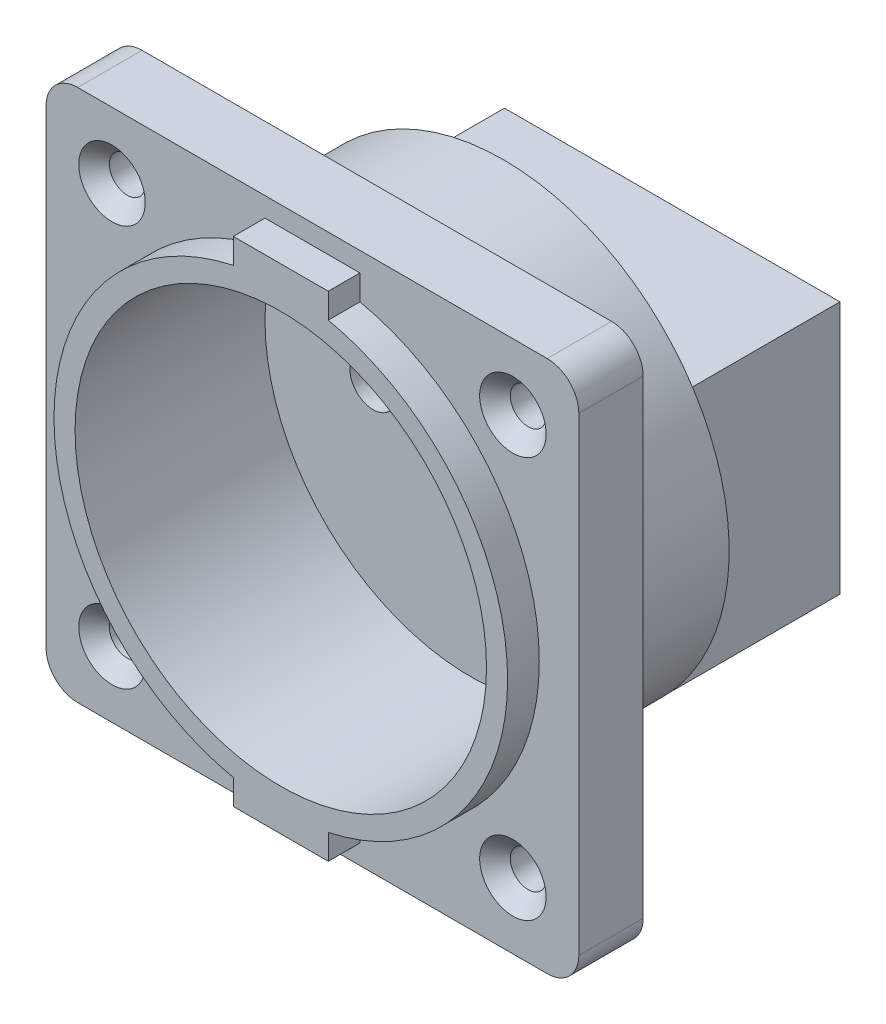
SolidWorks part; units mm, degrees
material "ABS"
ref_plane "Ebene vorne" through (0, 0, 0) normal (0, 0, 1) x (1, 0, 0)
ref_plane "Ebene oben" through (0, 0, 0) normal (0, 1, 0) x (1, 0, 0)
ref_plane "Ebene rechts" through (0, 0, 0) normal (1, 0, 0) x (0, 0, -1)
sketch "Skizze1" plane through (0, 0, 0) normal (0, 0, 1) x (1, 0, 0)
  line L1 (-25.25, -25.25) -> (25.25, -25.25)
  line L2 (-25.25, -25.25) -> (-25.25, 25.25)
  line L3 (-25.25, 25.25) -> (25.25, 25.25)
  line L4 (25.25, -25.25) -> (25.25, 25.25)
  line L5 (-25.25, -25.25) -> (25.25, 25.25) construction
  line L6 (-25.25, 25.25) -> (25.25, -25.25) construction
  point P0 (0, 0)
  dimension "D1" = 50.5
  dimension "D2" = 50.5
extrude "Aufsatz-Linear austragen1" add sketch "Skizze1" along normal blind 6.1
sketch "Skizze2" plane through (0, 0, 6.1) normal (0, 0, 1) x (1, 0, 0)
  line L0 (0, 23.4) -> (0, 0) construction
  line L1 (-4.5, 23.4) -> (4.5, 23.4)
  line L2 (-4.5, 23.4) -> (-4.5, -23.4)
  line L3 (-4.5, -23.4) -> (4.5, -23.4)
  line L4 (4.5, 23.4) -> (4.5, -23.4)
  line L5 (0, 0) -> (0, -23.4) construction
  circle A0 centre (0, 0) radius 21.5
  dimension "D1" = 43
  dimension "D2" = 9
  dimension "D3" = 46.8
extrude "Aufsatz-Linear austragen2" add sketch "Skizze2" along normal blind 3 contours L2 A0 | L4 A0 L2 | L4 A0 | A0 L4 L1 L2 | A0 L2 L3 L4 region at (0, 22.3661, 6.1) region at (0, 0, 6.1) region at (-11.6007, 0, 6.1) region at (11.6007, 0, 6.1) region at (0, -22.3661, 6.1)
sketch "Skizze3" plane through (0, 0, 0) normal (0, 0, -1) x (-1, 0, 0)
  circle A0 centre (0, 0) radius 21.4
  dimension "D1" = 42.8
extrude "Aufsatz-Linear austragen3" add sketch "Skizze3" along normal blind 12
sketch "Skizze4" plane through (0, 0, -12) normal (0, 0, -1) x (-1, 0, 0)
  line L0 (0, 0) -> (0, 9.6769) construction
  line L1 (-15.9, 9.6769) -> (15.9, 9.6769)
  line L2 (-15.9, 9.6769) -> (-15.9, -14.3231)
  line L3 (-15.9, -14.3231) -> (15.9, -14.3231)
  line L4 (15.9, 9.6769) -> (15.9, -14.3231)
  circle A0 centre (0, 0) radius 21.4 construction
  dimension "D1" = 31.8
  dimension "D2" = 24
extrude "Aufsatz-Linear austragen4" add sketch "Skizze4" along normal blind 16
hole_wizard "Formsenkung für M3 Linsensenkschraube mit Schlitz1" positions "Skizze5" profile "Skizze6" countersink size "M3" standard "DIN" end condition through all
sketch "Skizze5" plane through (0, 0, 6.1) normal (0, 0, 1) x (1, 0, 0)
  line L0 (-19, 19) -> (19, 19) construction
  line L1 (19, 19) -> (19, -19) construction
  line L2 (19, -19) -> (-19, -19) construction
  line L3 (-19, -19) -> (-19, 19) construction
  line L5 (0, 19) -> (0, 0) construction
  line L6 (0, 0) -> (0, -19) construction
  point P0 (-19, 19)
  point P2 (19, 19)
  point P4 (19, -19)
  point P6 (-19, -19)
  dimension "D1" = 38
sketch "Skizze6" plane through (-19, 19, 6.1) normal (1, 0, 0) x (0, -1, 0)
  line L0 (0, 0) -> (0, 34.1)
  line L1 (0, 34.1) -> (1.7, 34.1)
  line L2 (1.7, 34.1) -> (1.7, 1.45)
  line L3 (1.7, 1.45) -> (3.15, 0)
  line L5 (3.15, 0) -> (0, 0)
  line L6 (-1.7, 1.45) -> (-3.15, 0) construction
  line L11 (0, -6.35) -> (0, 107.95) construction
  dimension "Bohrerdurchmesser" = 3.4
  dimension "Bohrungstiefe" = 34.1
  dimension "Senkdurchmesser (Oben)" = 6.3
  dimension "Senkwinkel (Oben)" = 90
fillet "Verrundung1" radius 3 4 edges at (25.25, -25.25, 3.05) (25.25, 25.25, 3.05) (-25.25, -25.25, 3.05) (-25.25, 25.25, 3.05)
sketch "Skizze7" plane through (0, 0, 9.1) normal (0, 0, 1) x (1, 0, 0)
  circle A0 centre (0, 0) radius 19.5
  dimension "D1" = 39
extrude "Schnitt-Linear austragen1" cut sketch "Skizze7" against normal blind 18
hole_wizard "Ø4.4 (4.4) Durchmesser Bohrung1" positions "Skizze8" profile "Skizze9" hole size "Ø4.4" standard "DIN" end condition through all
sketch "Skizze8" plane through (0, 0, -8.9) normal (0, 0, 1) x (1, 0, 0)
  line L0 (-9.25, 0) -> (0, 0) construction
  line L1 (0, 0) -> (9.25, 0) construction
  point P0 (-9.25, 0)
  point P2 (9.25, 0)
  dimension "D1" = 18.5
sketch "Skizze9" plane through (-9.25, 0, -8.9) normal (1, 0, 0) x (0, -1, 0)
  line L0 (0, 0) -> (0, 19.1)
  line L1 (0, 19.1) -> (2.2, 19.1)
  line L2 (2.2, 19.1) -> (2.2, 0)
  line L5 (2.2, 0) -> (0, 0)
  line L11 (0, -6.35) -> (0, 107.95) construction
  dimension "Bohrerdurchmesser" = 4.4
  dimension "Bohrungstiefe" = 19.1
